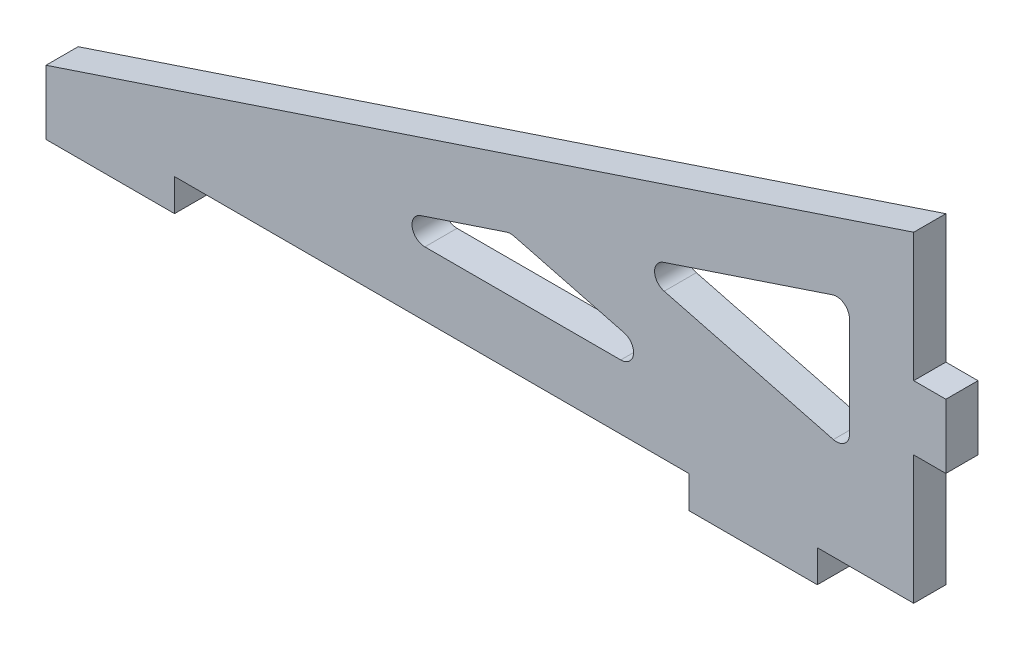
SolidWorks part; units mm, degrees
ref_plane "Front Plane" through (0, 0, 0) normal (0, 0, 1) x (1, 0, 0)
ref_plane "Top Plane" through (0, 0, 0) normal (0, 1, 0) x (1, 0, 0)
ref_plane "Right Plane" through (0, 0, 0) normal (1, 0, 0) x (0, 0, -1)
sketch "Sketch2" plane through (0, 0, 0) normal (0, 0, 1) x (1, 0, 0)
  line L0 (-92.95, 148.308) -> (78.5, 205.458)
  line L1 (78.5, 205.458) -> (84.85, 205.458) construction
  line L2 (84.85, 205.458) -> (84.85, 180.058) construction
  line L4 (-118.35, 135.608) -> (-118.35, 141.958) construction
  line L5 (84.85, 167.358) -> (84.85, 141.958) construction
  line L6 (84.85, 180.058) -> (78.5, 180.058)
  line L8 (84.85, 167.358) -> (78.5, 167.358)
  line L9 (78.5, 180.058) -> (78.5, 167.358) construction
  line L10 (-92.95, 135.608) -> (-92.95, 148.308) construction
  line L13 (-67.55, 141.958) -> (-67.55, 135.608)
  line L15 (34.05, 135.608) -> (34.05, 141.958)
  line L17 (59.45, 141.958) -> (59.45, 135.608)
  line L19 (-92.95, 135.608) -> (-118.35, 135.608) construction
  line L20 (-92.95, 141.958) -> (-92.95, 135.608)
  line L21 (-92.95, 141.958) -> (-92.95, 148.308)
  line L22 (-92.95, 135.608) -> (-67.55, 135.608)
  line L23 (-67.55, 141.958) -> (34.05, 141.958)
  line L24 (34.05, 135.608) -> (59.45, 135.608)
  line L25 (59.45, 141.958) -> (78.5, 141.958)
  line L26 (78.5, 167.358) -> (78.5, 141.958)
  line L27 (84.85, 167.358) -> (84.85, 180.058)
  line L28 (78.5, 180.058) -> (78.5, 205.458)
  line L29 (78.5, 265.783) -> (78.5, 141.958) construction
  dimension "D1" = 6.35
  dimension "D2" = 6.35
  dimension "D3" = 6.35
  dimension "D4" = 12.7
  dimension "D5" = 6.35
  dimension "D6" = 25.4
  dimension "D7" = 25.4
  dimension "D8" = 25.4
  dimension "D9" = 25.4
  dimension "D10" = 6.35
  dimension "D11" = 25.4
  dimension "D12" = 63.5
extrude "Boss-Extrude1" add sketch "Sketch2" along normal blind 6.35
sketch "Sketch3" plane through (0, 0, 6.35) normal (0, 0, 1) x (1, 0, 0)
  line L0 (-33.7391, 154.658) -> (65.8, 187.8377)
  line L1 (65.8, 187.8377) -> (65.8, 154.658)
  line L2 (65.8, 154.658) -> (-33.7391, 154.658)
  line L3 (78.5, 205.458) -> (-92.95, 148.308) construction
  line L4 (-67.55, 141.958) -> (34.05, 141.958) construction
  line L6 (65.8, 154.658) -> (-19.3713, 176.756) construction
  line L7 (64.2053, 148.5115) -> (-20.9661, 170.6095)
  line L8 (67.3947, 160.8045) -> (-17.7766, 182.9025)
  line L9 (78.5, 180.058) -> (78.5, 205.458) construction
  arc A0 (64.2053, 148.5115) -> (67.3947, 160.8045) centre (65.8, 154.658) ccw
  arc A1 (-17.7766, 182.9025) -> (-20.9661, 170.6095) centre (-19.3713, 176.756) ccw
  point P10 (23.2143, 165.707)
  dimension "D4" = 6.35
  dimension "D1" = 12.7
  dimension "D2" = 12.7
  dimension "D3" = 12.7
extrude "Cut-Extrude1" cut sketch "Sketch3" against normal through all contours L2 L7 L0 | L8 L1 L0 region at (1.8456, 158.2691, 6.35) region at (50.8315, 173.975, 6.35)
fillet "Fillet1" radius 2.54 6 edges at (65.8, 187.8377, 3.175) (20.8944, 172.8692, 3.175) (-1.2392, 165.4913, 3.175) (40.5151, 154.658, 3.175) (-33.7391, 154.658, 3.175) (65.8, 161.2182, 3.175)
